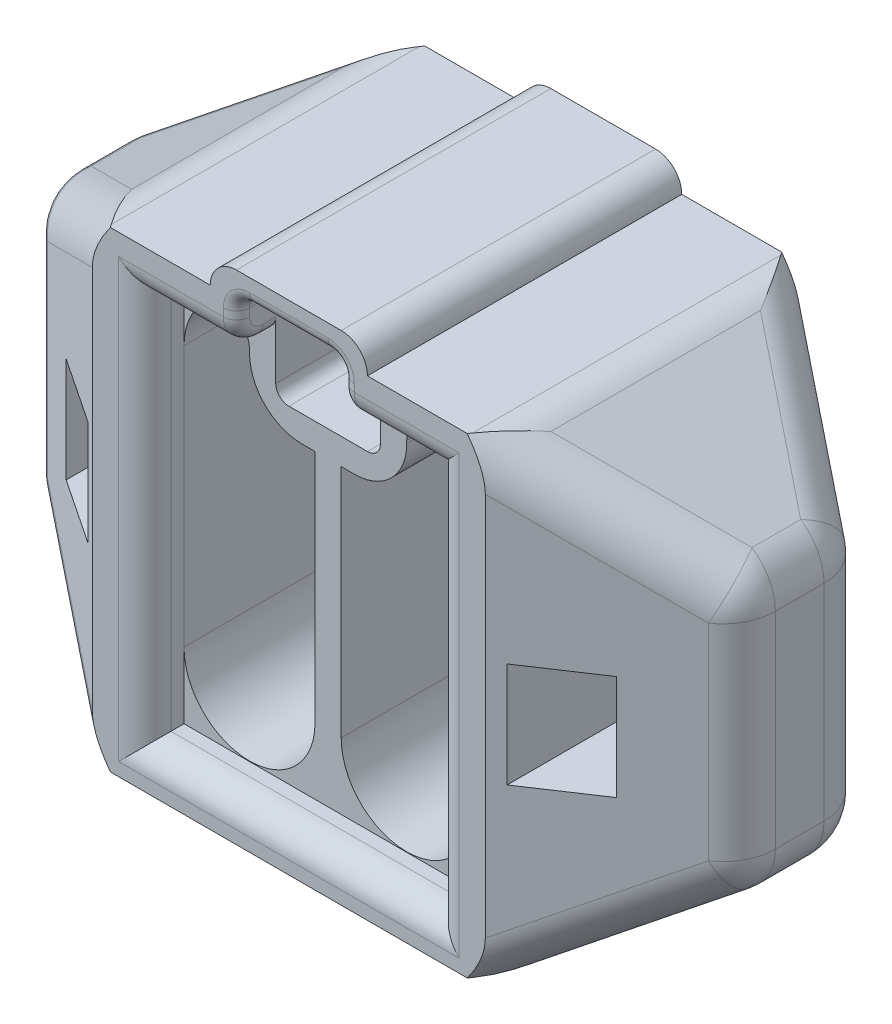
SolidWorks part; units mm, degrees
ref_plane "Front Plane" through (0, 0, 0) normal (0, 0, 1) x (1, 0, 0)
ref_plane "Top Plane" through (0, 0, 0) normal (0, 1, 0) x (1, 0, 0)
ref_plane "Right Plane" through (0, 0, 0) normal (1, 0, 0) x (0, 0, -1)
sketch "Sketch3" plane through (0, 0, 0) normal (0, 0, 1) x (1, 0, 0)
  line L0 (0, -12.0876) -> (0, 12.3723) construction
  line L1 (0.5, 5) -> (0.5, -5)
  line L2 (-5.5, 5) -> (-5.5, -5)
  line L3 (5.5, 5) -> (5.5, -5)
  line L4 (-0.5, 5) -> (-0.5, -5)
  line L5 (-5.5, 5) -> (-0.5, -5) construction
  line L6 (-5.5, -5) -> (-0.5, 5) construction
  line L8 (-7.5, -9) -> (7.5, -9)
  line L9 (-7.5, -9) -> (-7.5, 9)
  line L10 (-7.5, 9) -> (7.5, 9)
  line L11 (7.5, -9) -> (7.5, 9)
  line L12 (-7.5, -9) -> (7.5, 9) construction
  line L13 (-7.5, 9) -> (7.5, -9) construction
  arc A0 (-0.5, 5) -> (-5.5, 5) centre (-3, 5) ccw
  arc A1 (-5.5, -4.9643) -> (-0.5, -4.9643) centre (-3, -4.9821) ccw
  arc A2 (5.5, -4.9643) -> (0.5, -4.9643) centre (3, -4.9821) cw
  arc A3 (0.5, 5) -> (5.5, 5) centre (3, 5) cw
  point P0 (-3, 0)
  point P20 (0, 0)
  dimension "D1" = 5
  dimension "D2" = 10
  dimension "D3" = 0.5
  dimension "D4" = 18
  dimension "D5" = 2
extrude "Boss-Extrude1" add sketch "Sketch3" along normal blind 12 contours L8 L11 L10 L9 A1 L2 A0 L4 L1 A3 L3 A2 region at (0, -0.0094, 0)
sketch "Sketch6" plane through (0, 0, 0) normal (0, 0, -1) x (-1, 0, 0)
  line L1 (2, 5) -> (-2, 5)
  line L2 (2, 5) -> (2, 9)
  line L3 (2, 9) -> (-2, 9)
  line L4 (-2, 5) -> (-2, 9)
  line L5 (2, 5) -> (-2, 9) construction
  line L6 (2, 9) -> (-2, 5) construction
  point P0 (0, 7)
  dimension "D1" = 4
  dimension "D2" = 4
  dimension "D3" = 5
sketch "Sketch7" plane through (0, 0, 0) normal (0, 0, 1) x (1, 0, 0)
  line L1 (3, 10) -> (-3, 10)
  line L2 (3, 10) -> (3, 4)
  line L3 (3, 4) -> (-3, 4)
  line L4 (-3, 10) -> (-3, 4)
  line L5 (3, 10) -> (-3, 4) construction
  line L6 (3, 4) -> (-3, 10) construction
  point P0 (0, 7)
  dimension "D1" = 6
  dimension "D2" = 6
extrude "Boss-Extrude3" add sketch "Sketch7" along normal blind 12
fillet "Fillet6" radius 2 2 edges at (3, 4, 6) (-3, 4, 6)
fillet "Fillet7" radius 1 2 edges at (3, 7.5, 6) (-3, 7.5, 6)
fillet "Fillet8" radius 1 2 edges at (3, 10, 6) (-3, 10, 6)
sketch "Sketch8" plane through (0, 0, 12) normal (0, 0, 1) x (1, 0, 0)
  line L1 (-2, 9) -> (2, 9)
  line L2 (-2, 9) -> (-2, 5)
  line L3 (-2, 5) -> (2, 5)
  line L4 (2, 9) -> (2, 5)
  line L5 (-2, 9) -> (2, 5) construction
  line L6 (-2, 5) -> (2, 9) construction
  point P0 (0, 7)
extrude "Cut-Extrude3" cut sketch "Sketch8" against normal through all
fillet "Fillet9" radius 0.5 4 edges at (2, 5, 6) (2, 9, 6) (-2, 9, 6) (-2, 5, 6)
sketch "Sketch9" plane through (0, 0, 0) normal (0, 0, 1) x (1, 0, 0)
  line L0 (-7.5, -9) -> (-13.5, -5)
  line L1 (-13.5, -5) -> (-13.5, 5)
  line L2 (-13.5, 5) -> (-7.5, 9)
  line L3 (-7.5, 9) -> (-7.5, -9)
  line L4 (-7.5, 9) -> (-3, 9) construction
  line L5 (-10.5, -2.1895) -> (-8, -2.1895)
  line L6 (-10.5, -2.1895) -> (-10.5, 1.8105)
  line L7 (-10.5, 1.8105) -> (-8, 1.8105)
  line L8 (-8, -2.1895) -> (-8, 1.8105)
  line L9 (-10.5, -2.1895) -> (-8, 1.8105) construction
  line L10 (-10.5, 1.8105) -> (-8, -2.1895) construction
  point P6 (-9.25, -0.1895)
  dimension "D1" = 4
  dimension "D2" = 2.5
  dimension "D3" = 8
  dimension "D4" = 6
  dimension "D5" = 10
  dimension "D6" = 4
  dimension "D7" = 4
extrude "Boss-Extrude4" add sketch "Sketch9" along normal blind 12
sketch "Sketch10" plane through (0, -9, 0) normal (0, -1, 0) x (1, 0, 0)
  line L0 (-7.5, 12) -> (-13.5, 8)
  line L1 (-13.5, 12) -> (-13.5, 0) construction
  line L2 (-13.5, 8) -> (-13.5, 12)
  line L3 (-13.5, 12) -> (-7.5, 12)
  line L4 (-13.5, 0) -> (-13.5, 4)
  line L5 (-13.5, 4) -> (-7.5, 0)
  line L6 (-7.5, 0) -> (-13.5, 0)
  dimension "D1" = 4
  dimension "D2" = 4
extrude "Cut-Extrude4" cut sketch "Sketch10" against normal through all
mirror "Mirror3" about plane through (0, 0, 0) normal (1, 0, 0) of "Cut-Extrude4", "Boss-Extrude4"
sketch "Sketch12" plane through (0, -9, 0) normal (0, -1, 0) x (1, 0, 0)
  line L1 (-5.5001, 12) -> (5.5001, 12)
  line L2 (-5.5001, 12) -> (-5.5001, 10.5)
  line L3 (-5.5001, 10.5) -> (5.5001, 10.5)
  line L4 (5.5001, 12) -> (5.5001, 10.5)
  dimension "D1" = 1.5
extrude "Cut-Extrude6" cut sketch "Sketch12" against normal blind 14.7 from offset 1.5 offset against normal yes
fillet "Fillet16" radius 1 5 edges at (3.75, 7.2, 12) (5.5001, -0.15, 12) (0, -7.5, 12) (-3.75, 7.2, 12) (-5.5001, -0.15, 12)
fillet "Fillet17" radius 0.5 9 edges at (2, 7.2, 10.75) (2, 7.4929, 11.7071) (2, 8.35, 12) (1.8536, 8.8536, 12) (-2, 7.2, 10.75) (-2, 7.4929, 11.7071) (-2, 8.35, 12) (-1.8536, 8.8536, 12) (0, 9, 12)
fillet "Fillet19" radius 2 20 edges at (-7.5, 9, 6) (7.5, 9, 6) (10.5, 7, 2) (10.5, 7, 10) (13.5, 5, 6) (13.5, 0, 4) (13.5, 0, 8) (10.5, -7, 2) (10.5, -7, 10) (13.5, -5, 6) (7.5, -9, 6) (-7.5, -9, 6) (-13.5, 5, 6) (-10.5, 7, 2) (-10.5, -7, 2) (-13.5, 0, 4) (-13.5, -5, 6) (-10.5, 7, 10) (-13.5, 0, 8) (-10.5, -7, 10)
